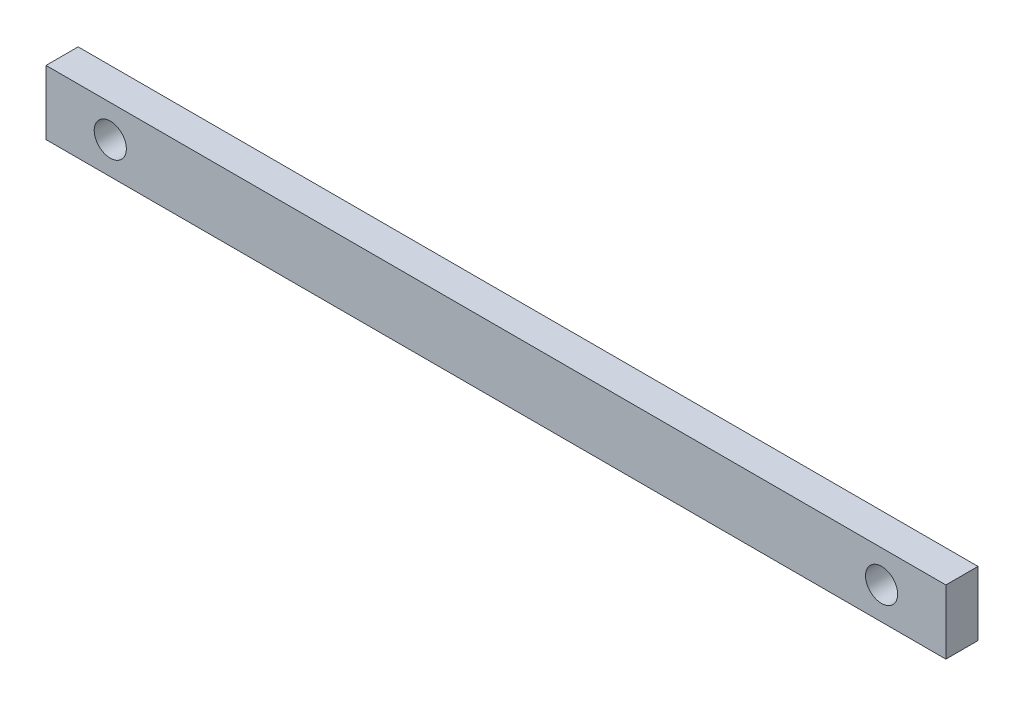
SolidWorks part; units mm, degrees
ref_plane "Front Plane" through (0, 0, 0) normal (0, 0, 1) x (1, 0, 0)
ref_plane "Top Plane" through (0, 0, 0) normal (0, 1, 0) x (1, 0, 0)
ref_plane "Right Plane" through (0, 0, 0) normal (1, 0, 0) x (0, 0, -1)
sketch "Sketch1" plane through (0, 0, 0) normal (0, 1, 0) x (1, 0, 0)
  line L0 (0, 0) -> (280, 0)
  line L1 (280, 0) -> (280, 10)
  line L2 (280, 10) -> (0, 10)
  line L3 (0, 10) -> (0, 0)
  dimension "D1" = 280
  dimension "D2" = 10
extrude "Boss-Extrude1" add sketch "Sketch1" along normal blind 20
sketch "Sketch2" plane through (0, 0, 0) normal (0, 0, 1) x (1, 0, 0)
  line L0 (0, 10) -> (20, 10)
  line L1 (0, 20) -> (0, 0) construction
  line L2 (280, 10) -> (260, 10)
  line L3 (280, 20) -> (280, 0) construction
  circle A0 centre (20, 10) radius 5
  circle A1 centre (260, 10) radius 5
  dimension "D1" = 20
  dimension "D2" = 20
extrude "Cut-Extrude1" cut sketch "Sketch2" against normal blind 56 contours A0 | A1 region at (20, 5.1414, 0) region at (255.1414, 10, 0)
